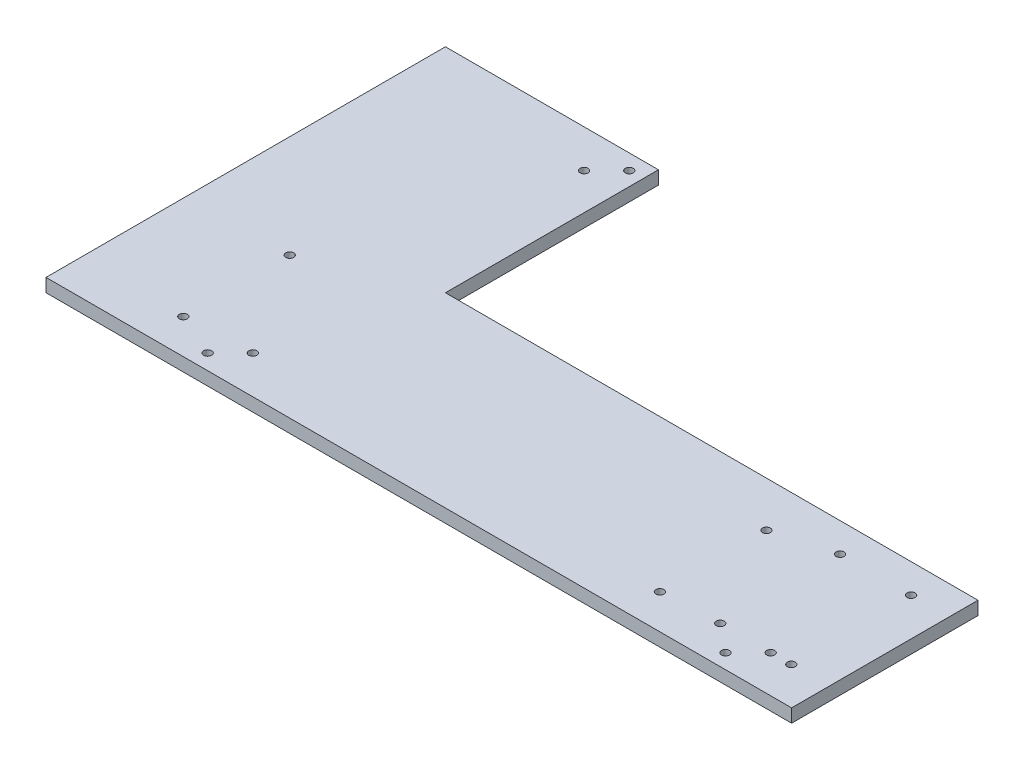
SolidWorks part; units mm, degrees
ref_plane "Front Plane" through (0, 0, 0) normal (0, 0, 1) x (1, 0, 0)
ref_plane "Top Plane" through (0, 0, 0) normal (0, 1, 0) x (1, 0, 0)
ref_plane "Right Plane" through (0, 0, 0) normal (1, 0, 0) x (0, 0, -1)
sketch "Sketch1" plane through (0, 0, 0) normal (0, 1, 0) x (1, 0, 0)
  line L1 (-124.5552, -60.7829) -> (155.4448, -60.7829)
  line L2 (-124.5552, -60.7829) -> (-124.5552, 9.2171)
  line L3 (-124.5552, 9.2171) -> (155.4448, 9.2171)
  line L4 (155.4448, -60.7829) -> (155.4448, 9.2171)
  line L6 (-124.5552, 9.2171) -> (-124.5552, 89.2171)
  line L7 (-124.5552, 89.2171) -> (-44.5552, 89.2171)
  line L8 (-44.5552, 9.2171) -> (-44.5552, 89.2171)
  circle A0 centre (141.2452, -46.6972) radius 1.5
  circle A1 centre (141.2452, -1.6972) radius 1.5
  circle A2 centre (114.5654, -1.6972) radius 1.5
  circle A3 centre (114.5654, -46.6972) radius 1.5
  circle A4 centre (92.978, -47.7829) radius 1.5
  circle A5 centre (92.978, -7.7829) radius 1.5
  circle A6 centre (-86.022, -47.7384) radius 1.5
  circle A7 centre (-86.022, -7.7829) radius 1.5
  circle A8 centre (-61.1247, -46.5403) radius 1.5
  circle A9 centre (-69.61, -55.0256) radius 1.5
  circle A10 centre (125.0964, -55.2612) radius 1.5
  circle A11 centre (133.5816, -46.7759) radius 1.5
  circle A12 centre (-49.7523, 83.4597) radius 1.5
  circle A13 centre (-58.2375, 74.9744) radius 1.5
  dimension "D5" = 3
  dimension "D6" = 3
  dimension "D7" = 3
  dimension "D8" = 3
  dimension "D9" = 3
  dimension "D10" = 3
  dimension "D11" = 3
  dimension "D12" = 3
  dimension "D13" = 3
  dimension "D14" = 3
  dimension "D1" = 280
  dimension "D2" = 70
  dimension "D3" = 80
  dimension "D4" = 150
extrude "Boss-Extrude1" add sketch "Sketch1" along normal blind 5 contours L1 L4 L3 L2 | L3 L8 L7 L6 region at (15.2753, 0, 25.7459) region at (-84.6228, 0, -49.1507)
